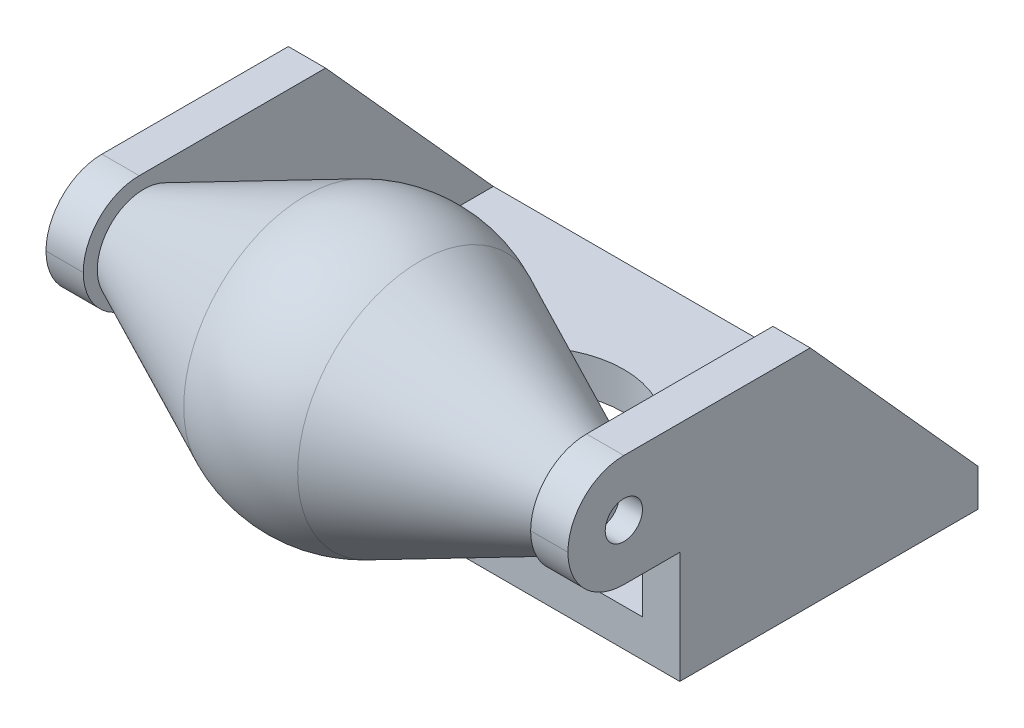
SolidWorks part; units mm, degrees
material "PP Homopolymer"
ref_plane "前视基准面" through (0, 0, 0) normal (0, 0, 1) x (1, 0, 0)
ref_plane "上视基准面" through (0, 0, 0) normal (0, 1, 0) x (1, 0, 0)
ref_plane "右视基准面" through (0, 0, 0) normal (1, 0, 0) x (0, 0, -1)
other "Configuration Table"
sketch "草图1" plane through (0, 0, 0) normal (0, 1, 0) x (1, 0, 0)
  line L1 (-14, -8) -> (14, -8)
  line L2 (-14, -8) -> (-14, 8)
  line L3 (-14, 8) -> (14, 8)
  line L4 (14, -8) -> (14, 8)
  line L5 (-14, -8) -> (14, 8) construction
  line L6 (-14, 8) -> (14, -8) construction
  point P0 (0, 0)
  dimension "D1" = 28
  dimension "D2" = 16
extrude "凸台-拉伸1" add sketch "草图1" along normal blind 2
sketch "草图2" plane through (-14, 0, 0) normal (-1, 0, 0) x (0, 0, 1)
  line L0 (-8, 0) -> (-8, 2)
  line L1 (-8, 2) -> (1, 12)
  line L2 (1, 12) -> (14, 12)
  line L4 (8, 2) -> (8, 0)
  line L5 (8, 0) -> (-8, 0)
  line L6 (14, 12) -> (14, 6)
  line L7 (14, 6) -> (8, 6)
  line L8 (8, 6) -> (8, 2)
  dimension "D1" = 13
  dimension "D2" = 9
  dimension "D3" = 12
  dimension "D4" = 6
extrude "凸台-拉伸2" add sketch "草图2" against normal blind 2
mirror "镜向1" about plane through (0, 0, 0) normal (1, 0, 0) of "凸台-拉伸2"
fillet "圆角1" radius 3 4 edges at (13, 6, 14) (13, 12, 14) (-13, 6, 14) (-13, 12, 14)
sketch "草图3" plane through (-14, 0, 0) normal (-1, 0, 0) x (0, 0, 1)
  circle A0 centre (11, 9) radius 1
  arc A1 (14, 9) -> (11, 12) centre (11, 9) ccw construction
  dimension "D1" = 2
extrude "切除-拉伸1" cut sketch "草图3" against normal through all
ref_plane "基准面1" through (0, 9, 0) normal (0, 1, 0) x (1, 0, 0)
sketch "草图4" plane through (0, 9, 0) normal (0, 1, 0) x (1, 0, 0)
  line L0 (-11.75, -11) -> (-11.75, -13.5)
  line L1 (-11.75, -13.5) -> (-3.0562, -17.554)
  line L2 (3.0562, -17.554) -> (11.75, -13.5)
  line L3 (11.75, -13.5) -> (11.75, -11)
  line L6 (-11.75, -11) -> (11.75, -11) construction
  line L7 (-12, -11) -> (-14, -11) construction
  line L8 (0, -11) -> (0, 0) construction
  line L9 (11.75, -11) -> (-11.75, -11)
  arc A0 (-3.0562, -17.554) -> (3.0562, -17.554) centre (0, -11) ccw
  dimension "D1" = 2.5
  dimension "D2" = 155
  dimension "D4" = 23.5
revolve "旋转2" add sketch "草图4" angle 360 about axis through (14, 9, 11) along (-1, 0, 0)
sketch "草图5" plane through (11.75, 0, 0) normal (1, 0, 0) x (0, 0, -1)
  line L0 (10.45, 9) -> (-10.45, 9) construction
  circle A0 centre (-11, 9) radius 1
  circle A1 centre (-11, 9) radius 1 construction
extrude "凸台-拉伸3" add sketch "草图5" along normal blind 1 and the other way blind 25
sketch "草图6" plane through (0, 0, 0) normal (0, -1, 0) x (1, 0, 0)
  line L0 (0, 0) -> (0, 8) construction
  line L1 (-14, 8) -> (14, 8) construction
  circle A0 centre (-8, 2) radius 2
  circle A1 centre (8, 2) radius 2
  circle A2 centre (0, 2) radius 5
  dimension "D1" = 4
  dimension "D2" = 16
  dimension "D4" = 10
  dimension "D3" = 6
extrude "切除-拉伸2" cut sketch "草图6" against normal blind 2
